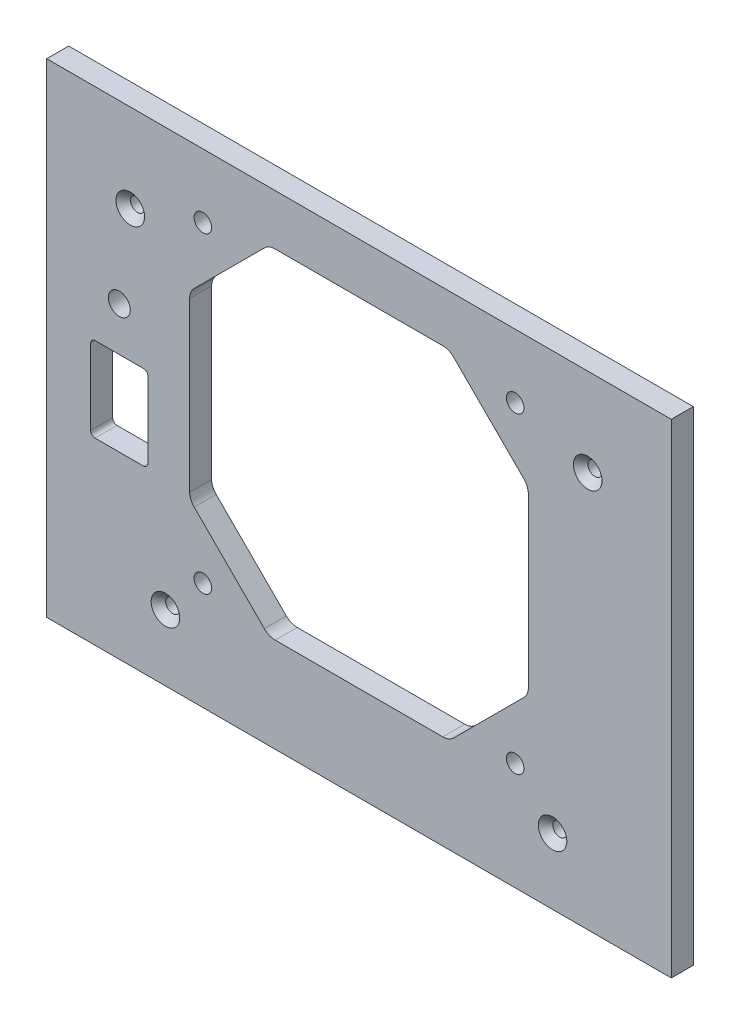
SolidWorks part; units mm, degrees
ref_plane "Front Plane" through (0, 0, 0) normal (0, 0, 1) x (1, 0, 0)
ref_plane "Top Plane" through (0, 0, 0) normal (0, 1, 0) x (1, 0, 0)
ref_plane "Right Plane" through (0, 0, 0) normal (1, 0, 0) x (0, 0, -1)
sketch "Sketch1" plane through (0, 0, 0) normal (0, 0, 1) x (1, 0, 0)
  line L1 (71, -55) -> (-71, -55)
  line L2 (71, -55) -> (71, 55)
  line L3 (71, 55) -> (-71, 55)
  line L4 (-71, -55) -> (-71, 55)
  line L5 (71, -55) -> (-71, 55) construction
  line L6 (71, 55) -> (-71, -55) construction
  point P0 (0, 0)
  dimension "D1" = 142
  dimension "D2" = 110
extrude "Boss-Extrude1" add sketch "Sketch1" along normal mid plane 5
sketch "Sketch7" plane through (0, 0, 2.5) normal (0, 0, 1) x (1, 0, 0)
  line L0 (-20.5, 43.5) -> (-38.5, 25.5)
  line L1 (20.5, -33.5) -> (-20.5, -33.5)
  line L2 (38.5, -15.5) -> (38.5, 25.5)
  line L3 (20.5, 43.5) -> (-20.5, 43.5)
  line L4 (-38.5, -15.5) -> (-38.5, 25.5)
  line L5 (38.5, -33.5) -> (-38.5, 43.5) construction
  line L6 (38.5, 43.5) -> (-38.5, -33.5) construction
  line L7 (-20.5, -33.5) -> (-38.5, -15.5)
  line L8 (38.5, -15.5) -> (20.5, -33.5)
  line L9 (38.5, 25.5) -> (20.5, 43.5)
  circle A0 centre (0, 5) radius 38.5 construction
  circle A1 centre (-35.5, -30.5) radius 2
  circle A2 centre (35.5, -30.5) radius 2
  circle A3 centre (35.5, 40.5) radius 2
  circle A4 centre (-35.5, 40.5) radius 2
  dimension "D3" = 4
  dimension "D10" = 77
  dimension "D2" = 5
  dimension "D4" = 71
  dimension "D5" = 71
  dimension "D11" = 77
extrude "Fan" cut sketch "Sketch7" against normal through all
chamfer "FanChamfer" [suppressed] distance 3 angle 45
fillet "Fillet1" radius 3.5 8 edges at (38.5, 25.5, 0) (38.5, -15.5, 0) (20.5, -33.5, 0) (-38.5, -15.5, 0) (-38.5, 25.5, 0) (-20.5, 43.5, 0) (20.5, 43.5, 0) (-20.5, -33.5, 0)
hole_wizard "Ø3.2 (3.2) Diameter Hole1" positions "Sketch9" profile "Sketch10" hole size "Ø3.2" standard "ANSI Metric" end condition through all
sketch "Sketch9" plane through (0, 0, 2.5) normal (0, 0, 1) x (1, 0, 0)
  line L0 (71, 55) -> (-71, 55) construction
  line L1 (-71, 55) -> (-71, -55) construction
  line L2 (71, -55) -> (71, 55) construction
  point P0 (-52, 35)
  point P2 (52, 35)
  dimension "D1" = 20
  dimension "D2" = 19
  dimension "D3" = 19
sketch "Sketch10" plane through (-52, 35, 2.5) normal (1, 0, 0) x (0, -1, 0)
  line L0 (0, 0) -> (0, 5)
  line L1 (0, 5) -> (1.6, 5)
  line L2 (1.6, 5) -> (1.6, 1.65)
  line L3 (1.6, 1.65) -> (3.25, 0)
  line L5 (3.25, 0) -> (0, 0)
  line L6 (-1.6, 1.65) -> (-3.25, 0) construction
  line L11 (0, -6.35) -> (0, 107.95) construction
  dimension "Thru Hole Dia." = 3.2
  dimension "Thru Hole Depth" = 5
  dimension "Near C'Sink Dia." = 6.5
  dimension "Near C'Sink Angle" = 90
hole_wizard "Ø3.2 (3.2) Diameter Hole2" positions "Sketch11" profile "Sketch12" hole size "Ø3.2" standard "ANSI Metric" end condition through all
sketch "Sketch11" plane through (0, 0, 2.5) normal (0, 0, 1) x (1, 0, 0)
  line L0 (-71, -55) -> (71, -55) construction
  line L1 (-71, 55) -> (-71, -55) construction
  line L2 (71, -55) -> (71, 55) construction
  point P0 (-44, -40)
  point P2 (44, -40)
  dimension "D1" = 15
  dimension "D2" = 27
  dimension "D3" = 27
sketch "Sketch12" plane through (-44, -40, 2.5) normal (1, 0, 0) x (0, -1, 0)
  line L0 (0, 0) -> (0, 5)
  line L1 (0, 5) -> (1.6, 5)
  line L2 (1.6, 5) -> (1.6, 1.65)
  line L3 (1.6, 1.65) -> (3.25, 0)
  line L5 (3.25, 0) -> (0, 0)
  line L6 (-1.6, 1.65) -> (-3.25, 0) construction
  line L11 (0, -6.35) -> (0, 107.95) construction
  dimension "Thru Hole Dia." = 3.2
  dimension "Thru Hole Depth" = 5
  dimension "Near C'Sink Dia." = 6.5
  dimension "Near C'Sink Angle" = 90
sketch "Sketch13" plane through (0, 0, 2.5) normal (0, 0, 1) x (1, 0, 0)
  line L0 (-71, 55) -> (-71, -55) construction
  line L1 (-60, 5) -> (-49, 5)
  line L2 (-61, 4) -> (-61, -13.2)
  line L3 (-60, -14.2) -> (-49, -14.2)
  line L4 (-48, 4) -> (-48, -13.2)
  line L5 (71, 55) -> (-71, 55) construction
  arc A0 (-49, -14.2) -> (-48, -13.2) centre (-49, -13.2) ccw
  arc A1 (-61, -13.2) -> (-60, -14.2) centre (-60, -13.2) ccw
  arc A2 (-49, 5) -> (-48, 4) centre (-49, 4) cw
  arc A3 (-60, 5) -> (-61, 4) centre (-60, 4) ccw
  point P8 (-61, -14.2)
  point P11 (-48, 5)
  point P14 (-61, 5)
  dimension "D3" = 1
  dimension "D1" = 13
  dimension "D2" = 19.2
  dimension "D4" = 10
  dimension "D5" = 50
extrude "Cut-Extrude1" cut sketch "Sketch13" against normal through all
sketch "Sketch8" plane through (0, 0, 2.5) normal (0, 0, 1) x (1, 0, 0)
  line L0 (-49, 5) -> (-60, 5) construction
  line L1 (71, 55) -> (-71, 55) construction
  circle A0 centre (-54.5, 15) radius 2.5
  point P2 (-47.2145, 0)
  point P3 (-54.1039, 14.8756)
  point P7 (-54.5, 5)
  dimension "D1" = 40
  dimension "D2" = 5
extrude "LEDHole" cut sketch "Sketch8" against normal through all
equation "\"D3@Sketch9\"=\"D2@Sketch9\""
equation "\"D3@Sketch11\"=\"D2@Sketch11\""
